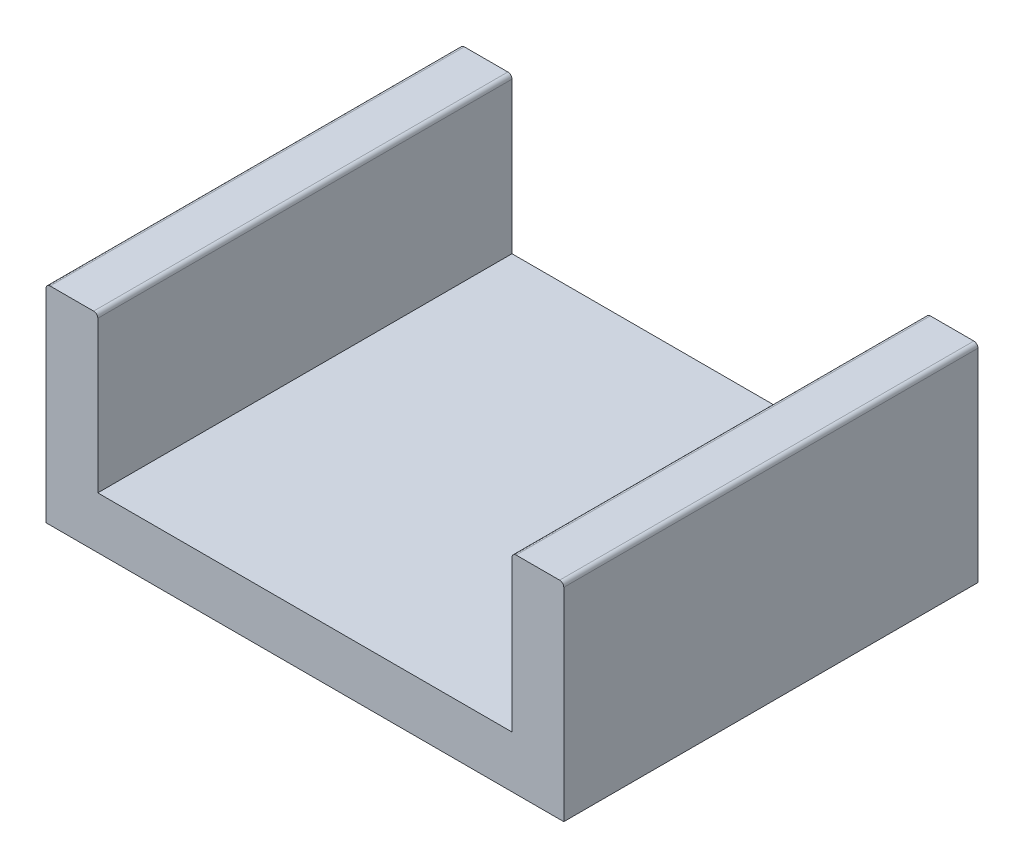
SolidWorks part; units mm, degrees
ref_plane "Front Plane" through (0, 0, 0) normal (0, 0, 1) x (1, 0, 0)
ref_plane "Top Plane" through (0, 0, 0) normal (0, 1, 0) x (1, 0, 0)
ref_plane "Right Plane" through (0, 0, 0) normal (1, 0, 0) x (0, 0, -1)
sketch "Sketch1" plane through (0, 0, 0) normal (0, 0, 1) x (1, 0, 0)
  line L0 (0, 0) -> (0, 12.7)
  line L1 (0, 12.7) -> (3.175, 12.7)
  line L2 (0, 0) -> (31.75, 0)
  line L3 (31.75, 0) -> (31.75, 12.7)
  line L4 (31.75, 12.7) -> (28.575, 12.7)
  line L5 (3.175, 12.7) -> (3.175, 3.175)
  line L6 (3.175, 3.175) -> (28.575, 3.175)
  line L7 (28.575, 3.175) -> (28.575, 12.7)
  dimension "D1" = 31.75
  dimension "D2" = 12.7
  dimension "D3" = 3.175
extrude "Boss-Extrude1" add sketch "Sketch1" along normal blind 25.4
fillet "Fillet1" radius 0.254 4 edges at (31.75, 12.7, 12.7) (28.575, 12.7, 12.7) (0, 12.7, 12.7) (3.175, 12.7, 12.7)
